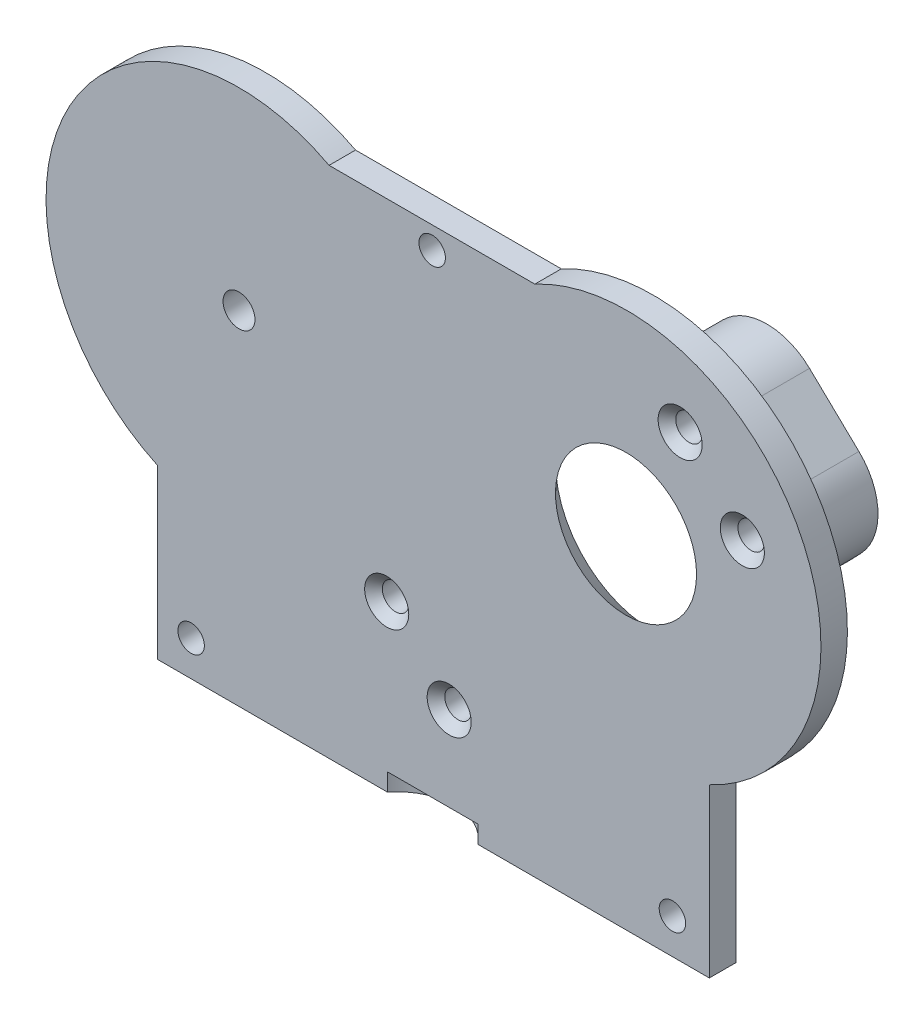
SolidWorks part; units mm, degrees
ref_plane "Alzado" through (0, 0, 0) normal (0, 0, 1) x (1, 0, 0)
ref_plane "Planta" through (0, 0, 0) normal (0, 1, 0) x (1, 0, 0)
ref_plane "Vista lateral" through (0, 0, 0) normal (1, 0, 0) x (0, 0, -1)
sketch "Croquis1" plane through (0, 0, 0) normal (0, 0, 1) x (1, 0, 0)
  line L0 (-41.1649, 0) -> (39.3505, 0) construction
  line L2 (-11.7855, 19.3588) -> (11.6637, 19.3588)
  line L4 (-31.2462, -19.8396) -> (-31.2462, -38.8969)
  line L5 (-31.2462, -38.8969) -> (31.3391, -38.8969)
  line L6 (31.3391, -19.8011) -> (31.3391, -38.8969)
  circle A0 centre (22, 0) radius 1.8101
  circle A1 centre (-22, 0) radius 1.8101
  arc A2 (-11.7855, 19.3588) -> (-31.2462, -19.8396) centre (-22, 0) ccw
  arc A3 (31.3391, -19.9194) -> (11.5484, 19.3588) centre (22, 0) ccw
  circle A4 centre (-22, 0) radius 22 construction
  circle A5 centre (22, 0) radius 22 construction
  dimension "D1" = 22
  dimension "D2" = 22
extrude "Base Soporte" add sketch "Croquis1" along normal blind 3 contours A3 L2 A2 L4 L5 L6 A1 A0 region at (0.0732, -7.7292, 0)
sketch "Croquis2" plane through (0, 0, 3) normal (0, 0, 1) x (1, 0, 0)
  line L0 (22, 27.9334) -> (22, -45.7501) construction
  line L1 (47.4237, 0) -> (-18.2884, 0) construction
  line L2 (-9.916, -31.8451) -> (44.0959, 22.1667) construction
  line L3 (-17.295, -13.0309) -> (8.571, -38.8969) construction
  line L4 (19.9459, 26.0957) -> (48.2465, -2.2049) construction
  line L5 (-18.6441, -25.0476) -> (35.2418, 28.8383) construction
  line L6 (49.9643, 12.7882) -> (-3.016, -40.1922) construction
  line L7 (-31.2462, -38.8969) -> (31.3391, -38.8969) construction
  line L8 (-11.9612, -18.3647) -> (3.4251, -33.751)
  line L9 (3.4251, -33.751) -> (41.6089, 4.4328)
  line L10 (41.6089, 4.4328) -> (26.2226, 19.8191)
  line L11 (26.2226, 19.8191) -> (-11.9612, -18.3647)
  point P0 (22, 0)
  dimension "D1" = 45
  dimension "D2" = 37
  dimension "D3" = 17
  dimension "D4" = 10.9783
  dimension "D5" = 10.7812
extrude "Cajeado Servo" cut sketch "Croquis2" against normal up to surface (3 mm away) up to face at (0.0104, -9.7803, 0)
sketch "Croquis3" plane through (0, 0, 0) normal (0, 0, -1) x (-1, 0, 0)
  line L0 (-26.2226, 19.8191) -> (-41.6089, 4.4328) construction
  line L1 (11.9612, -18.3647) -> (-26.2226, 19.8191) construction
  line L2 (-41.6089, 4.4328) -> (-3.4251, -33.751) construction
  line L3 (-26.2226, 19.8191) -> (-41.6089, 4.4328)
  line L4 (11.9612, -18.3647) -> (7.365, -13.7685)
  line L5 (-41.6089, 4.4328) -> (-37.0127, -0.1634)
  line L6 (15.7796, -18.3647) -> (9.2742, -11.8593)
  line L7 (-29.005, 20.855) -> (-42.855, 7.005)
  line L8 (-43.8181, 2.8236) -> (-38.9219, -2.0726)
  line L9 (-3.4251, -33.751) -> (11.9612, -18.3647) construction
  line L10 (-3.4251, -33.751) -> (11.9612, -18.3647)
  line L11 (-3.4251, -37.5694) -> (15.7796, -18.3647)
  line L12 (-40.7808, -3.9316) -> (-15.204, 21.6453) construction
  line L13 (-13.1472, -34.2807) -> (17.7274, -3.4061) construction
  line L14 (-38.9219, -2.0726) -> (-37.0127, -0.1634)
  line L15 (-21.6264, 15.2229) -> (-19.7172, 17.1321)
  line L16 (-9.9305, -31.064) -> (-8.0213, -29.1548)
  line L17 (7.365, -13.7685) -> (9.2742, -11.8593)
  line L18 (-19.7172, 17.1321) -> (-24.4484, 21.8633)
  line L19 (-21.6264, 15.2229) -> (-26.2226, 19.8191)
  line L20 (15.7796, -18.3647) -> (-26.2226, 23.6375) construction
  line L21 (-8.0213, -29.1548) -> (-3.4251, -33.751)
  line L22 (11.9612, -18.3647) -> (-26.2226, 19.8191) construction
  line L23 (-9.9305, -31.064) -> (-3.4251, -37.5694)
  line L24 (-41.6089, 4.4328) -> (-3.4251, -33.751) construction
  line L26 (-45.4272, 4.4328) -> (-3.4251, -37.5694) construction
  line L27 (-26.2226, 23.6375) -> (-45.4272, 4.4328) construction
  arc A0 (-11.5484, 19.3588) -> (-31.3391, -19.9194) centre (-22, 0) ccw construction
  arc A1 (-11.5484, 19.3588) -> (-15.7544, 21.0948) centre (-22, 0) ccw
  arc A2 (-24.4484, 21.8633) -> (-29.005, 20.855) centre (-22, 0) ccw
  arc A3 (-42.855, 7.005) -> (-43.8181, 2.8236) centre (-22, 0) ccw
  line M1 (-41.6089, 4.4328) -> (-26.2226, 19.8191)
  line M2 (-26.2226, 19.8191) -> (11.9612, -18.3647)
  line M3 (11.9612, -18.3647) -> (-3.4251, -33.751)
  line M4 (-3.4251, -33.751) -> (-41.6089, 4.4328)
  arc M10 (-11.5484, 19.3588) -> (-31.3391, -19.9194) centre (-22, 0) ccw
  dimension "D2" = 6.5
  dimension "D3" = 6.5
  dimension "D1" = 2.7
extrude "Soportes del Servo" add sketch "Croquis3" along normal blind 11 contours L15 L18 L7 L8 L14 M10 M4 M1 M2 | L16 L23 L11 L6 L17 M2 M3 M4 region at (34.1559, 12.3661, 0) region at (-8.5767, -13.071, 0)
sketch "Croquis4" plane through (0, 0, -11) normal (0, 0, -1) x (-1, 0, 0)
  line L0 (-35.0813, 5.9649) -> (-32.5887, 3.4724) construction
  line L1 (-19.7172, 17.1321) -> (-24.4484, 21.8633) construction
  line L2 (-29.005, 20.855) -> (-42.855, 7.005) construction
  line L3 (-43.8181, 2.8236) -> (-38.9219, -2.0726) construction
  line L4 (-28.029, 13.0548) -> (-25.5176, 10.5434) construction
  line L5 (-34.0018, 8.7294) -> (-30.7529, 11.8112)
  line L6 (-25.9117, 10.9375) -> (-19.7172, 17.1321)
  line L9 (-9.9305, -31.064) -> (-3.4251, -37.5694) construction
  line L10 (-3.4251, -37.5694) -> (15.7796, -18.3647) construction
  line L11 (15.7796, -18.3647) -> (9.2742, -11.8593) construction
  line L16 (-38.9219, -2.0726) -> (-32.9828, 3.8664)
  line L17 (-19.7172, 17.1321) -> (-24.4484, 21.8633)
  line L18 (-29.005, 20.855) -> (-42.855, 7.005)
  line L19 (-43.8181, 2.8236) -> (-38.9219, -2.0726)
  line L20 (-9.9305, -31.064) -> (9.2742, -11.8593)
  line L21 (-48.7658, -7.7196) -> (-15.8586, 25.1876) construction
  line L22 (-18.7964, -44.2182) -> (18.5052, -6.9165) construction
  line L25 (-9.9305, -31.064) -> (-3.4251, -37.5694)
  line L26 (-3.4251, -37.5694) -> (15.7796, -18.3647)
  line L27 (15.7796, -18.3647) -> (9.2742, -11.8593)
  line L32 (-5.0343, 2.8236) -> (-29.005, -21.1472) construction
  line L33 (-46.6062, 24.5609) -> (14.5071, -36.5524) construction
  arc A0 (-24.4484, 21.8633) -> (-29.005, 20.855) centre (-22, 0) ccw construction
  arc A1 (-42.855, 7.005) -> (-43.8181, 2.8236) centre (-22, 0) ccw construction
  arc A2 (-24.4484, 21.8633) -> (-29.005, 20.855) centre (-22, 0) ccw
  arc A3 (-42.855, 7.005) -> (-43.8181, 2.8236) centre (-22, 0) ccw
  circle A4 centre (-35.0813, 5.9649) radius 1.5
  circle A5 centre (-28.029, 13.0548) radius 1.5
  circle A6 centre (-1.8365, -27.2798) radius 1.5
  circle A7 centre (5.2489, -20.2232) radius 1.5
  arc A8 (-32.9828, 3.8664) -> (-34.0018, 8.7294) centre (-35.0813, 5.9649) ccw
  arc A9 (-30.7529, 11.8112) -> (-25.9117, 10.9375) centre (-28.029, 13.0548) ccw
  dimension "D2" = 5
  dimension "D1" = 47
  dimension "D3" = 5
  dimension "D4" = 5
  dimension "D5" = 5
extrude "Soportes Taladros servo" add sketch "Croquis4" along normal blind 3
sketch "Croquis5" plane through (0, 0, 3) normal (0, 0, 1) x (1, 0, 0)
  circle A2 centre (-0.0936, 16.8559) radius 1.5
  circle A3 centre (-27.4327, -34.8986) radius 1.5
  circle A4 centre (27.1527, -34.8986) radius 1.5
extrude "Taladros tapa" cut sketch "Croquis5" against normal up to surface (3 mm away) up to face at (-20.1899, 0, 0)
sketch "Croquis6" plane through (0, 0, 3) normal (0, 0, 1) x (1, 0, 0)
  line L1 (26.2226, 19.8191) -> (-11.9612, -18.3647) construction
  line L2 (-11.9612, -18.3647) -> (3.4251, -33.751) construction
  line L3 (3.4251, -33.751) -> (41.6089, 4.4328) construction
  line L4 (41.6089, 4.4328) -> (26.2226, 19.8191) construction
  line L5 (-7.1617, -13.5652) -> (-11.9612, -18.3647)
  line L6 (26.2226, 19.8191) -> (21.4604, 15.057)
  line L7 (-11.9612, -18.3647) -> (3.4251, -33.751)
  line L8 (3.4251, -33.751) -> (8.2246, -28.9515)
  line L9 (41.6089, 4.4328) -> (26.2226, 19.8191)
  line L10 (21.4604, 15.057) -> (36.8467, -0.3294)
  line L11 (-7.1617, -13.5652) -> (8.2246, -28.9515)
  line L12 (36.8467, -0.3294) -> (41.6089, 4.4328)
  circle A0 centre (-5.2489, -20.2232) radius 1.5 construction
  circle A1 centre (35.0813, 5.9649) radius 1.5 construction
  circle A2 centre (28.029, 13.0548) radius 1.5 construction
  circle A3 centre (-5.2489, -20.2232) radius 1.5
  circle A4 centre (35.0813, 5.9649) radius 1.5
  circle A5 centre (28.029, 13.0548) radius 1.5
  circle A6 centre (1.8365, -27.2798) radius 1.5 construction
  circle A7 centre (1.8365, -27.2798) radius 1.5
extrude "Rectificacion Taladros Servos" add sketch "Croquis6" against normal up to surface (3 mm away) up to face at (28.6527, -34.8986, 0)
sketch "Croquis7" plane through (20.4972, -20.4972, 0) normal (0.7071, -0.7071, 0) x (0, 0, -1)
  line L0 (0, -49.5987) -> (0, -5.3442) construction
  line L1 (0, -49.5987) -> (0, 41.9541)
  line L2 (0, 41.9541) -> (24.9895, 41.9541)
  line L3 (24.9895, 41.9541) -> (24.9895, -49.5987)
  line L4 (24.9895, -49.5987) -> (0, -49.5987)
extrude "Suprimir soporte servo" cut sketch "Croquis7" against normal up to surface (27.1595 mm away)
sketch "Croquis8" plane through (0, 0, 0) normal (0, 0, -1) x (-1, 0, 0)
  line L2 (7.1617, -13.5652) -> (-8.2246, -28.9515) construction
  line L3 (-36.8467, -0.3294) -> (-21.4604, 15.057) construction
  line L4 (-42.8649, 5.9649) -> (-27.1413, 20.9986)
  line L6 (7.1617, -13.5652) -> (-8.2246, -28.9515)
  line L7 (-36.8467, -0.3294) -> (-21.4604, 15.057)
  line L8 (-21.4604, 15.057) -> (-27.1413, 20.9986)
  line L9 (-36.8467, -0.3294) -> (-42.8649, 5.9649)
  line L10 (-8.2246, -28.9515) -> (-1.8365, -35.6327)
  line L11 (-1.8365, -35.6327) -> (13.887, -20.5991)
  line L12 (7.1617, -13.5652) -> (13.887, -20.5991)
  circle A0 centre (-35.0813, 5.9649) radius 1.5 construction
  circle A1 centre (-28.029, 13.0548) radius 1.5 construction
  circle A2 centre (-1.8365, -27.2798) radius 1.5 construction
  circle A3 centre (5.2489, -20.2232) radius 1.5 construction
  circle A5 centre (-35.0813, 5.9649) radius 1.5
  circle A6 centre (-28.029, 13.0548) radius 1.5
  circle A7 centre (-1.8365, -27.2798) radius 1.5
  circle A8 centre (5.2489, -20.2232) radius 1.5
extrude "Rectificación Soporte servo" add sketch "Croquis8" along normal blind 7.5
fillet "Redondeo soporte servo" radius 7 4 edges at (1.8365, -35.6327, -3.75) (-13.887, -20.5991, -3.75) (42.8649, 5.9649, -3.75) (27.1413, 20.9986, -3.75)
sketch "Croquis9" plane through (0, 0, -7.5) normal (0, 0, -1) x (-1, 0, 0)
  line L0 (-40.3293, 18.5395) -> (11.8074, -33.5972) construction
  line L1 (-1.3084, 6.5868) -> (-28.4092, -20.5139) construction
  line L2 (-34.8104, 11.6064) -> (-33.3962, 13.0206)
  line L4 (-34.8104, 11.6064) -> (-29.8607, 6.6567)
  line L5 (-36.8467, -0.3294) -> (-21.4604, 15.057) construction
  line L6 (-29.8607, 6.6567) -> (-28.4465, 8.0709)
  line L7 (-28.4465, 8.0709) -> (-33.3962, 13.0206)
  line L8 (0.1757, -20.5513) -> (5.1254, -25.501)
  line L9 (-1.2385, -21.9655) -> (0.1757, -20.5513)
  line L10 (3.7112, -26.9152) -> (-1.2385, -21.9655)
  line L11 (3.7112, -26.9152) -> (5.1254, -25.501)
extrude "Rectif caja soporte servo" cut sketch "Croquis9" against normal blind 2.5
sketch "Croquis10" plane through (0, 0, 3) normal (0, 0, 1) x (1, 0, 0)
  line L0 (-41.2766, 0.0044) -> (39.2389, 0.0044) construction
  line L1 (21.4604, 15.057) -> (-7.1617, -13.5652) construction
  line L2 (21.4604, 15.057) -> (36.8467, -0.3294) construction
  line L3 (8.2246, -28.9515) -> (36.8467, -0.3294) construction
  line L4 (8.2246, -28.9515) -> (-7.1617, -13.5652) construction
  line L5 (11.4368, 19.3633) -> (11.5521, 19.3633)
  line L7 (21.4604, 15.057) -> (-7.1617, -13.5652)
  line L8 (21.4604, 15.057) -> (36.8467, -0.3294)
  line L9 (8.2246, -28.9515) -> (36.8467, -0.3294)
  line L10 (8.2246, -28.9515) -> (-7.1617, -13.5652)
  circle A6 centre (21.8884, 0.0044) radius 7
  line M1 (36.8467, -0.3294) -> (8.2246, -28.9515)
  line M2 (8.2246, -28.9515) -> (-7.1617, -13.5652)
  line M3 (-7.1617, -13.5652) -> (21.4604, 15.057)
  line M4 (21.4604, 15.057) -> (36.8467, -0.3294)
extrude "Rectificación  hueco servo" add sketch "Croquis10" against normal up to surface (3 mm away) contours L0 L8 A6 M3 M2 M1 | L7 L0 A6 M4 region at (14.1722, 7.2927, 3) region at (11.3053, -12.1763, 3) up to face at (-1.7076, -14.7501, 0)
chamfer "Chaflán hueco servo" distance 4 angle 45 1 edges at (28.8884, 0.0044, 0)
chamfer "Chaflán Taladros servo" distance 1 angle 45 4 edges at (-3.7489, -20.2232, 3) (3.3365, -27.2798, 3) (29.529, 13.0548, 3) (36.5813, 5.9649, 3)
sketch "Croquis11" plane through (0, -38.8969, 0) normal (0, -1, 0) x (1, 0, 0)
  line L0 (-31.794, 7) -> (31.6992, 7) construction
  line L1 (0, -11.8514) -> (0, 24.3862) construction
  line L2 (-31.2462, 3) -> (31.3391, 3) construction
  circle A0 centre (-0.0474, 7) radius 6.5
  dimension "D1" = 4
extrude "Caja servo exterior" cut sketch "Croquis11" against normal blind 2
